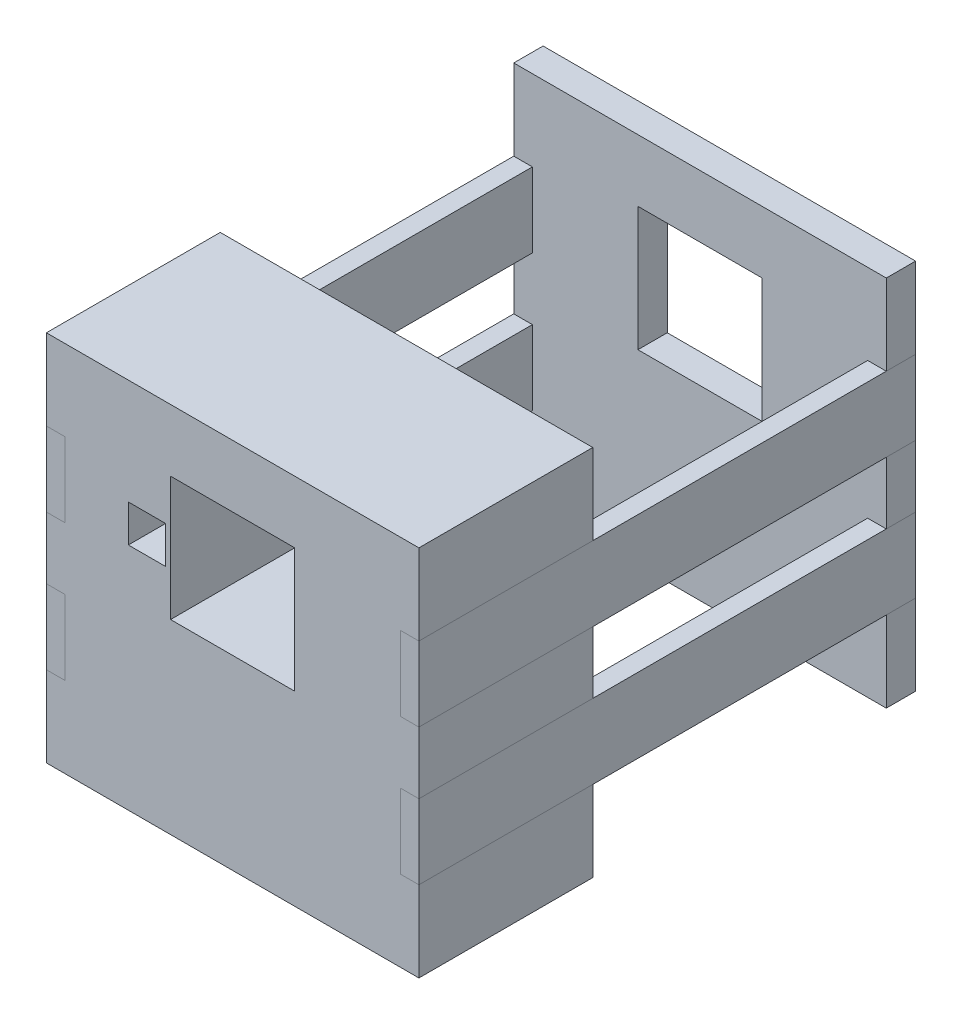
SolidWorks part; units mm, degrees
material "Balsa"
ref_plane "Front Plane" through (0, 0, 0) normal (0, 0, 1) x (1, 0, 0)
ref_plane "Top Plane" through (0, 0, 0) normal (0, 1, 0) x (1, 0, 0)
ref_plane "Right Plane" through (0, 0, 0) normal (1, 0, 0) x (0, 0, -1)
sketch "Sketch1" plane through (0, 0, 0) normal (0, 0, 1) x (1, 0, 0)
  line L1 (0, 0) -> (38.1, 0)
  line L2 (0, 0) -> (0, 38.1)
  line L3 (0, 38.1) -> (38.1, 38.1)
  line L4 (38.1, 0) -> (38.1, 38.1)
  dimension "D1" = 38.1
  dimension "box" = 38.1
extrude "Boss-Extrude1" add sketch "Sketch1" against normal blind 17.78
sketch "Sketch2" plane through (0, 0, 0) normal (0, 0, 1) x (1, 0, 0)
  line L0 (0, 19.05) -> (38.1, 19.05) construction
  line L1 (0, 0) -> (0, 38.1) construction
  line L2 (38.1, 0) -> (38.1, 38.1) construction
  line L3 (19.05, 0) -> (19.05, 38.1) construction
  line L4 (0, 0) -> (38.1, 0) construction
  line L5 (0, 38.1) -> (38.1, 38.1) construction
  line L6 (38.1, 22.225) -> (36.195, 22.225)
  line L7 (12.7, 31.75) -> (25.4, 31.75)
  line L8 (12.7, 31.75) -> (12.7, 19.05)
  line L9 (12.7, 19.05) -> (25.4, 19.05)
  line L10 (25.4, 31.75) -> (25.4, 19.05)
  line L11 (0, 29.845) -> (1.905, 29.845)
  line L12 (0, 29.845) -> (0, 22.225)
  line L13 (0, 22.225) -> (1.905, 22.225)
  line L14 (1.905, 29.845) -> (1.905, 22.225)
  line L15 (36.195, 29.845) -> (36.195, 22.225)
  line L16 (38.1, 29.845) -> (36.195, 29.845)
  line L17 (38.1, 29.845) -> (38.1, 22.225)
  line L18 (38.1, 8.255) -> (38.1, 15.875)
  line L19 (38.1, 8.255) -> (36.195, 8.255)
  line L20 (36.195, 8.255) -> (36.195, 15.875)
  line L21 (38.1, 15.875) -> (36.195, 15.875)
  line L22 (0, 15.875) -> (1.905, 15.875)
  line L23 (1.905, 8.255) -> (1.905, 15.875)
  line L24 (0, 8.255) -> (1.905, 8.255)
  line L25 (0, 8.255) -> (0, 15.875)
  line L27 (12.192, 27.305) -> (8.382, 27.305)
  line L28 (12.192, 27.305) -> (12.192, 23.495)
  line L29 (12.192, 23.495) -> (8.382, 23.495)
  line L30 (8.382, 27.305) -> (8.382, 23.495)
  point P36 (12.192, 25.4)
  dimension "D1" = 12.7
  dimension "D2" = 12.7
  dimension "D3" = 12.7
  dimension "D4" = 12.7
  dimension "D5" = 3.175
  dimension "D6" = 7.62
  dimension "D7" = 1.905
  dimension "D8" = 3.81
  dimension "D9" = 0.508
  dimension "D10" = 3.81
  dimension "D11" = 4.445
extrude "Cut-Extrude1" cut sketch "Sketch2" against normal blind 20.32
ref_plane "Plane1" through (0, 0, -50.8) normal (0, 0, 1) x (1, 0, 0)
sketch "Sketch3" plane through (0, 0, -50.8) normal (0, 0, 1) x (1, 0, 0)
  line L0 (12.7, 19.05) -> (25.4, 19.05) construction
  line L1 (25.4, 19.05) -> (25.4, 31.75) construction
  line L2 (25.4, 31.75) -> (12.7, 31.75) construction
  line L3 (12.7, 31.75) -> (12.7, 19.05) construction
  line L4 (12.7, 19.05) -> (25.4, 19.05)
  line L5 (25.4, 19.05) -> (25.4, 31.75)
  line L6 (25.4, 31.75) -> (12.7, 31.75)
  line L7 (12.7, 31.75) -> (12.7, 19.05)
  line L20 (38.1, 15.875) -> (38.1, 22.225)
  line L21 (38.1, 22.225) -> (36.195, 22.225)
  line L22 (36.195, 22.225) -> (36.195, 29.845)
  line L23 (36.195, 29.845) -> (38.1, 29.845)
  line L24 (38.1, 29.845) -> (38.1, 38.1)
  line L25 (38.1, 38.1) -> (0, 38.1)
  line L26 (0, 38.1) -> (0, 29.845)
  line L27 (0, 29.845) -> (1.905, 29.845)
  line L28 (1.905, 29.845) -> (1.905, 22.225)
  line L29 (1.905, 22.225) -> (0, 22.225)
  line L30 (0, 22.225) -> (0, 15.875)
  line L31 (0, 15.875) -> (1.905, 15.875)
  line L32 (1.905, 15.875) -> (1.905, 8.255)
  line L33 (1.905, 8.255) -> (0, 8.255)
  line L34 (0, 8.255) -> (0, 0)
  line L35 (0, 0) -> (38.1, 0)
  line L36 (38.1, 0) -> (38.1, 8.255)
  line L37 (38.1, 8.255) -> (36.195, 8.255)
  line L38 (36.195, 8.255) -> (36.195, 15.875)
  line L39 (36.195, 15.875) -> (38.1, 15.875)
  line L40 (38.1, 15.875) -> (38.1, 22.225)
  line L41 (38.1, 22.225) -> (36.195, 22.225)
  line L42 (36.195, 22.225) -> (36.195, 29.845)
  line L43 (36.195, 29.845) -> (38.1, 29.845)
  line L44 (38.1, 29.845) -> (38.1, 38.1)
  line L45 (38.1, 38.1) -> (0, 38.1)
  line L46 (0, 38.1) -> (0, 29.845)
  line L47 (0, 29.845) -> (1.905, 29.845)
  line L48 (1.905, 29.845) -> (1.905, 22.225)
  line L49 (1.905, 22.225) -> (0, 22.225)
  line L50 (0, 22.225) -> (0, 15.875)
  line L51 (0, 15.875) -> (1.905, 15.875)
  line L52 (1.905, 15.875) -> (1.905, 8.255)
  line L53 (1.905, 8.255) -> (0, 8.255)
  line L54 (0, 8.255) -> (0, 0)
  line L55 (0, 0) -> (38.1, 0)
  line L56 (38.1, 0) -> (38.1, 8.255)
  line L57 (38.1, 8.255) -> (36.195, 8.255)
  line L58 (36.195, 8.255) -> (36.195, 15.875)
  line L59 (36.195, 15.875) -> (38.1, 15.875)
  dimension "D1" = 0
extrude "Boss-Extrude2" add sketch "Sketch3" along normal blind 3 separate body
sketch "Sketch6" plane through (1.905, 0, 0) normal (-1, 0, 0) x (0, 0, 1)
  line L0 (-17.78, 29.845) -> (-17.78, 22.225) construction
  line L1 (-17.78, 38.1) -> (0, 38.1) construction
  circle A0 centre (-8.89, 27.2143) radius 1.27
  dimension "D2" = 2.54
  dimension "D1" = 8.89
  dimension "D3" = 10.8857
extrude "SpringPlunger Hole" cut sketch "Sketch6" against normal blind 3 contours A0
sketch "Sketch8" plane through (0, 0, 0) normal (0, 0, 1) x (1, 0, 0)
  line L0 (38.1, 0) -> (38.1, 38.1) construction
  line L1 (36.195, 22.225) -> (38.1, 22.225) construction
  line L2 (38.1, 29.845) -> (36.195, 29.845) construction
  line L3 (36.195, 29.845) -> (36.195, 22.225) construction
  line L4 (36.195, 8.255) -> (38.1, 8.255) construction
  line L5 (38.1, 15.875) -> (36.195, 15.875) construction
  line L6 (36.195, 15.875) -> (36.195, 8.255) construction
  line L7 (0, 8.255) -> (1.905, 8.255) construction
  line L8 (1.905, 8.255) -> (1.905, 15.875) construction
  line L9 (1.905, 15.875) -> (0, 15.875) construction
  line L10 (0, 22.225) -> (1.905, 22.225) construction
  line L11 (1.905, 22.225) -> (1.905, 29.845) construction
  line L12 (1.905, 29.845) -> (0, 29.845) construction
  line L13 (0, 0) -> (0, 38.1) construction
  line L14 (38.1, 8.255) -> (38.1, 15.875)
  line L15 (36.195, 22.225) -> (38.1, 22.225)
  line L16 (38.1, 29.845) -> (36.195, 29.845)
  line L17 (36.195, 29.845) -> (36.195, 22.225)
  line L18 (36.195, 8.255) -> (38.1, 8.255)
  line L19 (38.1, 15.875) -> (36.195, 15.875)
  line L20 (36.195, 15.875) -> (36.195, 8.255)
  line L21 (0, 8.255) -> (1.905, 8.255)
  line L22 (1.905, 8.255) -> (1.905, 15.875)
  line L23 (1.905, 15.875) -> (0, 15.875)
  line L24 (0, 22.225) -> (1.905, 22.225)
  line L25 (1.905, 22.225) -> (1.905, 29.845)
  line L26 (1.905, 29.845) -> (0, 29.845)
  line L27 (0, 8.255) -> (0, 15.875)
  line L28 (0, 22.225) -> (0, 29.845)
  line L29 (38.1, 22.225) -> (38.1, 29.845)
extrude "Support" add sketch "Sketch8" against normal up to surface (50.8 mm away) contours L26 L28 L24 L25 | L21 L22 L23 L27 | L16 L17 L15 L29 | L14 L19 L20 L18 up to face at (19.05, 19.05, -50.8)
equation "\"box\"= 1.5"
equation "\"D1@Sketch1\"=\"box\""
equation "\"shaft\"= 0.5"
equation "\"D1@Sketch2\"=\"shaft\""
equation "\"D2@Sketch2\"=\"shaft\""
equation "\"D4@Sketch2\"=\"shaft\""
equation "\"D3@Sketch2\"=(\"box\"-\"shaft\")/2"
equation "\"D5@Sketch2\"=\"shaft\"/4"
equation "\"D6@Sketch2\"=\"box\"*0.2"
equation "\"D7@Sketch2\"=\"D6@Sketch2\"/4"
equation "\"springHole\"=0.15"
equation "\"D8@Sketch2\"=\"springHole\""
equation "\"D10@Sketch2\"=\"D8@Sketch2\""
equation "\"D11@Sketch2\"=\"D2@Sketch2\"/2-\"D8@Sketch2\"/2"
equation "\"depth1\"=0.7"
equation "\"D1@Boss-Extrude1\"=\"depth1\""
equation "\"D1@Sketch6\"=\"depth1\"/2"
equation "\"springPinDiameter\"=0.1"
equation "\"D2@Sketch6\"=\"springPinDiameter\""
equation "\"D3@Sketch6\"=\"box\"/3.5"
